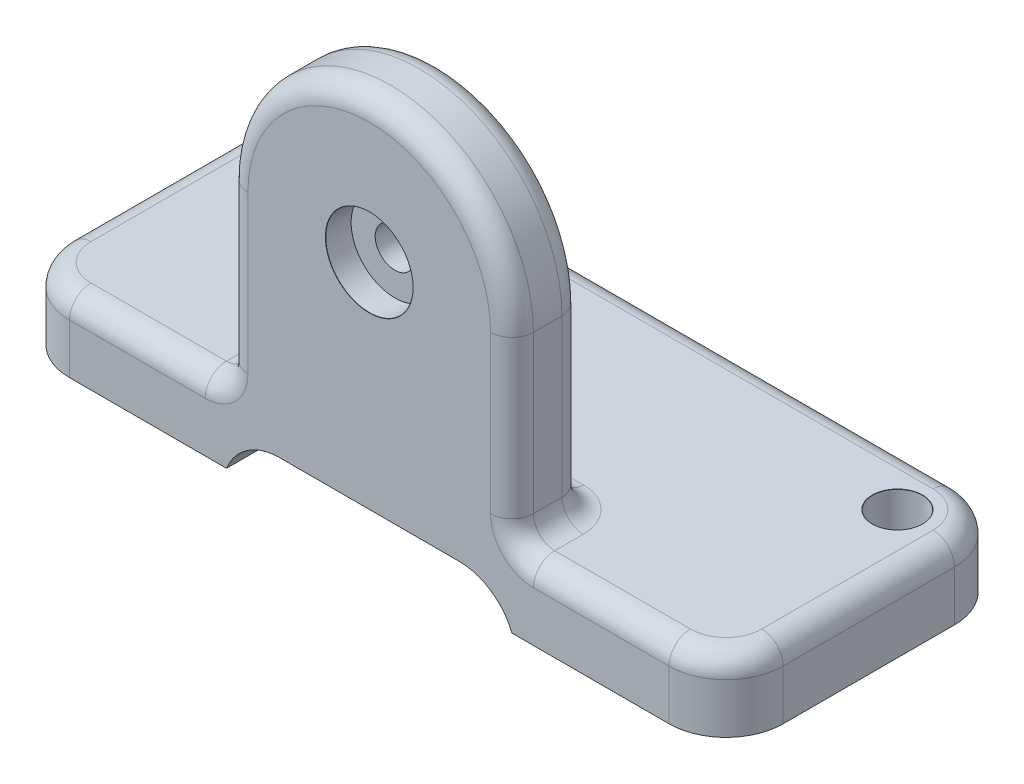
SolidWorks part; units mm, degrees
ref_plane "Plano frontal" through (0, 0, 0) normal (0, 0, 1) x (1, 0, 0)
ref_plane "Plano superior" through (0, 0, 0) normal (0, 1, 0) x (1, 0, 0)
ref_plane "Plano direito" through (0, 0, 0) normal (1, 0, 0) x (0, 0, -1)
sketch "Esboço1" plane through (0, 0, 0) normal (0, 1, 0) x (1, 0, 0)
  line L1 (0, 0) -> (100, 0)
  line L2 (0, 0) -> (0, 40)
  line L3 (0, 40) -> (100, 40)
  line L4 (100, 0) -> (100, 40)
  dimension "D1" = 40
  dimension "D2" = 100
extrude "Ressalto-extrusão1" add sketch "Esboço1" along normal blind 10
sketch "Esboço3" plane through (0, 0, 0) normal (0, 0, 1) x (1, 0, 0)
  line L0 (0, 0) -> (100, 0) construction
  line L1 (30, 0) -> (30, 35)
  line L2 (70, 35) -> (70, 0)
  line L3 (70, 0) -> (30, 0)
  line L4 (0, 10) -> (0, 0) construction
  arc A0 (30, 35) -> (70, 35) centre (50, 35) cw
  point P6 (0, 0)
  point P7 (0, 0)
  dimension "D2" = 20
  dimension "D1" = 35
  dimension "D3" = 50
extrude "Ressalto-extrusão2" add sketch "Esboço3" against normal blind 10
sketch "Esboço4" plane through (0, 0, 0) normal (0, 0, 1) x (1, 0, 0)
  line L0 (30, 35) -> (30, 10) construction
  line L5 (70, 10) -> (70, 35) construction
  line L15 (0, 0) -> (100, 0) construction
  line L16 (30, 0) -> (70, 0)
  line L17 (30, 0) -> (30, 5.0139)
  line L18 (30, 5.0139) -> (70, 5.0139)
  line L19 (70, 0) -> (70, 5.0139)
  dimension "D1" = 5.0139
extrude "Corte-extrusão1" cut sketch "Esboço4" against normal through all
hole_wizard "Rebaixo para parafuso de cabeça sextavada de M51" positions "Esboço5" profile "Esboço6" counterbore size "M5" standard "Ansi Metric" end condition through all
sketch "Esboço5" plane through (0, 0, 0) normal (0, 0, 1) x (1, 0, 0)
  point P0 (50, 35)
sketch "Esboço6" plane through (50, 35, 0) normal (1, 0, 0) x (0, -1, 0)
  line L0 (0, 0) -> (0, 40)
  line L1 (0, 40) -> (2.75, 40)
  line L3 (2.75, 40) -> (2.75, 3.58)
  line L4 (6.12, 3.58) -> (2.75, 3.58)
  line L5 (6.12, 3.58) -> (6.12, 0.025)
  line L6 (6.12, 0.025) -> (6.145, 0)
  line L7 (6.145, 0) -> (0, 0)
  line L8 (-6.12, 0.025) -> (-6.145, 0) construction
  line L11 (0, -6.35) -> (0, 107.95) construction
  dimension "Thru Hole Dia." = 5.5
  dimension "Thru Hole Depth" = 40
  dimension "C'Bore Dia." = 12.24
  dimension "C'Bore Depth" = 3.58
  dimension "Near C'Sink Dia." = 12.29
  dimension "Near C'Sink Angle" = 90
fillet "Filete1" radius 8 6 edges at (0, 5, -40) (0, 5, 0) (100, 5, -40) (100, 5, 0) (70, 5.0139, -20) (30, 5.0139, -20)
hole_wizard "Furo de diâmetro Ø7.0 (7)1" positions "Esboço9" profile "Esboço10" hole size "Ø7.0" standard "Ansi Metric" end condition through all
sketch "Esboço9" plane through (0, 10, 0) normal (0, 1, 0) x (1, 0, 0)
  point P0 (8, 32)
  point P3 (92, 32)
sketch "Esboço10" plane through (8, 10, -32) normal (1, 0, 0) x (0, 0, 1)
  line L0 (0, 0) -> (0, 10)
  line L1 (0, 10) -> (3.5, 10)
  line L2 (3.5, 10) -> (3.5, 0.025)
  line L3 (3.5, 0.025) -> (3.525, 0)
  line L5 (3.525, 0) -> (0, 0)
  line L6 (-3.5, 0.025) -> (-3.525, 0) construction
  line L11 (0, -6.35) -> (0, 107.95) construction
  dimension "Thru Hole Dia." = 7
  dimension "Thru Hole Depth" = 10
  dimension "Near C'Sink Dia." = 7.05
  dimension "Near C'Sink Angle" = 90
fillet "Filete2" radius 3 18 edges at (70, 22.5, -10) (30, 22.5, -10) (70, 22.5, 0) (30, 22.5, 0) (50, 55, -10) (50, 55, 0) (81, 10, 0) (97.6569, 10, -2.3431) (100, 10, -20) (97.6569, 10, -37.6569) (19, 10, 0) (2.3431, 10, -2.3431) (0, 10, -20) (2.3431, 10, -37.6569) (50, 10, -40) (30, 10, -5) (50, 10, -10) (70, 10, -5)
